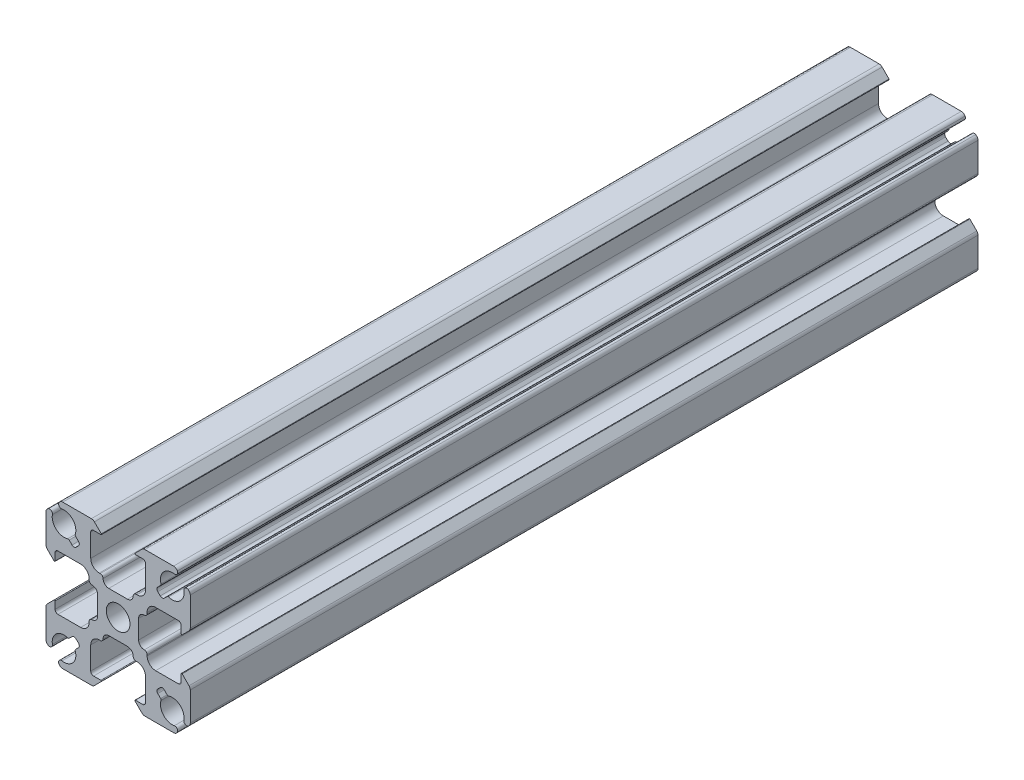
SolidWorks part; units mm, degrees
ref_plane "Front Plane" through (0, 0, 0) normal (0, 0, 1) x (1, 0, 0)
ref_plane "Top Plane" through (0, 0, 0) normal (0, 1, 0) x (1, 0, 0)
ref_plane "Right Plane" through (0, 0, 0) normal (1, 0, 0) x (0, 0, -1)
ref_plane "Plane1" through (0, 0, 0) normal (0, 0, -1) x (-1, 0, 0)
sketch "Sketch1" plane through (0, 0, 0) normal (0, 0, -1) x (-1, 0, 0)
  line L0 (-7.4885, 8.6199) -> (-6.9856, 8.117)
  line L1 (-6.9856, 7.4099) -> (-7.4099, 6.9856)
  line L2 (-8.117, 6.9856) -> (-8.6199, 7.4885)
  line L3 (-12.7, 9.7594) -> (-12.7, 4.7107)
  line L4 (-12.4803, 4.1803) -> (-11.2707, 2.9707)
  line L5 (-11.1, 3.0414) -> (-11.1, 4.325)
  line L6 (-10.6, 4.825) -> (-6.6, 4.825)
  line L7 (-5.1, 3.325) -> (-5.1, 3.15)
  line L8 (-3.6, 1.65) -> (-3.6, -1.65)
  line L9 (-5.1, -3.15) -> (-5.1, -3.325)
  line L10 (-6.6, -4.825) -> (-10.6, -4.825)
  line L11 (-11.1, -4.325) -> (-11.1, -3.0414)
  line L12 (-11.2707, -2.9707) -> (-12.4803, -4.1803)
  line L13 (-12.7, -4.7107) -> (-12.7, -9.7594)
  line L14 (-8.6199, -7.4885) -> (-8.117, -6.9856)
  line L15 (-7.4099, -6.9856) -> (-6.9856, -7.4099)
  line L16 (-6.9856, -8.117) -> (-7.4885, -8.6199)
  line L17 (-9.7594, -12.7) -> (-4.7107, -12.7)
  line L18 (-4.1803, -12.4803) -> (-2.9707, -11.2707)
  line L19 (-3.0414, -11.1) -> (-4.325, -11.1)
  line L20 (-4.825, -10.6) -> (-4.825, -6.6)
  line L21 (-3.325, -5.1) -> (-3.15, -5.1)
  line L22 (-1.65, -3.6) -> (1.65, -3.6)
  line L23 (3.15, -5.1) -> (3.325, -5.1)
  line L24 (4.825, -6.6) -> (4.825, -10.6)
  line L25 (4.325, -11.1) -> (3.0414, -11.1)
  line L26 (2.9707, -11.2707) -> (4.1803, -12.4803)
  line L27 (4.7107, -12.7) -> (9.7594, -12.7)
  line L28 (7.4885, -8.6199) -> (6.9856, -8.117)
  line L29 (6.9856, -7.4099) -> (7.4099, -6.9856)
  line L30 (8.117, -6.9856) -> (8.6199, -7.4885)
  line L31 (12.7, -9.7594) -> (12.7, -4.7107)
  line L32 (12.4803, -4.1803) -> (11.2707, -2.9707)
  line L33 (11.1, -3.0414) -> (11.1, -4.325)
  line L34 (10.6, -4.825) -> (6.6, -4.825)
  line L35 (5.1, -3.325) -> (5.1, -3.15)
  line L36 (3.6, -1.65) -> (3.6, 1.65)
  line L37 (5.1, 3.15) -> (5.1, 3.325)
  line L38 (6.6, 4.825) -> (10.6, 4.825)
  line L39 (11.1, 4.325) -> (11.1, 3.0414)
  line L40 (11.2707, 2.9707) -> (12.4803, 4.1803)
  line L41 (12.7, 4.7107) -> (12.7, 9.7594)
  line L42 (8.6199, 7.4885) -> (8.117, 6.9856)
  line L43 (7.4099, 6.9856) -> (6.9856, 7.4099)
  line L44 (6.9856, 8.117) -> (7.4885, 8.6199)
  line L45 (9.7594, 12.7) -> (4.7107, 12.7)
  line L46 (4.1803, 12.4803) -> (2.9707, 11.2707)
  line L47 (3.0414, 11.1) -> (4.325, 11.1)
  line L48 (4.825, 10.6) -> (4.825, 6.6)
  line L49 (3.325, 5.1) -> (3.15, 5.1)
  line L50 (1.65, 3.6) -> (-1.65, 3.6)
  line L51 (-3.15, 5.1) -> (-3.325, 5.1)
  line L52 (-4.825, 6.6) -> (-4.825, 10.6)
  line L53 (-4.325, 11.1) -> (-3.0414, 11.1)
  line L54 (-2.9707, 11.2707) -> (-4.1803, 12.4803)
  line L55 (-4.7107, 12.7) -> (-9.7594, 12.7)
  circle A0 centre (0, 0) radius 2.08
  arc A1 (-9.7594, 12.7) -> (-10.4266, 12.2927) centre (-9.7594, 11.95) ccw
  arc A2 (-10.4266, 12.2927) -> (-9.8933, 11.5721) centre (-9.9818, 12.0642) ccw
  arc A3 (-9.8933, 11.5721) -> (-7.5492, 8.8748) centre (-9.525, 9.525) cw
  arc A4 (-7.5492, 8.8748) -> (-7.4885, 8.6199) centre (-7.3118, 8.7967) ccw
  arc A5 (-6.9856, 8.117) -> (-6.9856, 7.4099) centre (-7.3392, 7.7635) cw
  arc A6 (-7.4099, 6.9856) -> (-8.117, 6.9856) centre (-7.7635, 7.3392) cw
  arc A7 (-8.6199, 7.4885) -> (-8.8748, 7.5492) centre (-8.7967, 7.3118) ccw
  arc A8 (-8.8748, 7.5492) -> (-11.5721, 9.8933) centre (-9.525, 9.525) cw
  arc A9 (-11.5721, 9.8933) -> (-12.2927, 10.4266) centre (-12.0642, 9.9818) ccw
  arc A10 (-12.2927, 10.4266) -> (-12.7, 9.7594) centre (-11.95, 9.7594) ccw
  arc A11 (-12.7, 4.7107) -> (-12.4803, 4.1803) centre (-11.95, 4.7107) ccw
  arc A12 (-11.2707, 2.9707) -> (-11.1, 3.0414) centre (-11.2, 3.0414) ccw
  arc A13 (-11.1, 4.325) -> (-10.6, 4.825) centre (-10.6, 4.325) cw
  arc A14 (-6.6, 4.825) -> (-5.1, 3.325) centre (-6.6, 3.325) cw
  arc A15 (-5.1, 3.15) -> (-4.6, 2.65) centre (-4.6, 3.15) ccw
  arc A16 (-4.6, 2.65) -> (-3.6, 1.65) centre (-4.6, 1.65) cw
  arc A17 (-3.6, -1.65) -> (-4.6, -2.65) centre (-4.6, -1.65) cw
  arc A18 (-4.6, -2.65) -> (-5.1, -3.15) centre (-4.6, -3.15) ccw
  arc A19 (-5.1, -3.325) -> (-6.6, -4.825) centre (-6.6, -3.325) cw
  arc A20 (-10.6, -4.825) -> (-11.1, -4.325) centre (-10.6, -4.325) cw
  arc A21 (-11.1, -3.0414) -> (-11.2707, -2.9707) centre (-11.2, -3.0414) ccw
  arc A22 (-12.4803, -4.1803) -> (-12.7, -4.7107) centre (-11.95, -4.7107) ccw
  arc A23 (-12.7, -9.7594) -> (-12.2927, -10.4266) centre (-11.95, -9.7594) ccw
  arc A24 (-12.2927, -10.4266) -> (-11.5721, -9.8933) centre (-12.0642, -9.9818) ccw
  arc A25 (-11.5721, -9.8933) -> (-8.8748, -7.5492) centre (-9.525, -9.525) cw
  arc A26 (-8.8748, -7.5492) -> (-8.6199, -7.4885) centre (-8.7967, -7.3118) ccw
  arc A27 (-8.117, -6.9856) -> (-7.4099, -6.9856) centre (-7.7635, -7.3392) cw
  arc A28 (-6.9856, -7.4099) -> (-6.9856, -8.117) centre (-7.3392, -7.7635) cw
  arc A29 (-7.4885, -8.6199) -> (-7.5492, -8.8748) centre (-7.3118, -8.7967) ccw
  arc A30 (-7.5492, -8.8748) -> (-9.8933, -11.5721) centre (-9.525, -9.525) cw
  arc A31 (-9.8933, -11.5721) -> (-10.4266, -12.2927) centre (-9.9818, -12.0642) ccw
  arc A32 (-10.4266, -12.2927) -> (-9.7594, -12.7) centre (-9.7594, -11.95) ccw
  arc A33 (-4.7107, -12.7) -> (-4.1803, -12.4803) centre (-4.7107, -11.95) ccw
  arc A34 (-2.9707, -11.2707) -> (-3.0414, -11.1) centre (-3.0414, -11.2) ccw
  arc A35 (-4.325, -11.1) -> (-4.825, -10.6) centre (-4.325, -10.6) cw
  arc A36 (-4.825, -6.6) -> (-3.325, -5.1) centre (-3.325, -6.6) cw
  arc A37 (-3.15, -5.1) -> (-2.65, -4.6) centre (-3.15, -4.6) ccw
  arc A38 (-2.65, -4.6) -> (-1.65, -3.6) centre (-1.65, -4.6) cw
  arc A39 (1.65, -3.6) -> (2.65, -4.6) centre (1.65, -4.6) cw
  arc A40 (2.65, -4.6) -> (3.15, -5.1) centre (3.15, -4.6) ccw
  arc A41 (3.325, -5.1) -> (4.825, -6.6) centre (3.325, -6.6) cw
  arc A42 (4.825, -10.6) -> (4.325, -11.1) centre (4.325, -10.6) cw
  arc A43 (3.0414, -11.1) -> (2.9707, -11.2707) centre (3.0414, -11.2) ccw
  arc A44 (4.1803, -12.4803) -> (4.7107, -12.7) centre (4.7107, -11.95) ccw
  arc A45 (9.7594, -12.7) -> (10.4266, -12.2927) centre (9.7594, -11.95) ccw
  arc A46 (10.4266, -12.2927) -> (9.8933, -11.5721) centre (9.9818, -12.0642) ccw
  arc A47 (9.8933, -11.5721) -> (7.5492, -8.8748) centre (9.525, -9.525) cw
  arc A48 (7.5492, -8.8748) -> (7.4885, -8.6199) centre (7.3118, -8.7967) ccw
  arc A49 (6.9856, -8.117) -> (6.9856, -7.4099) centre (7.3392, -7.7635) cw
  arc A50 (7.4099, -6.9856) -> (8.117, -6.9856) centre (7.7635, -7.3392) cw
  arc A51 (8.6199, -7.4885) -> (8.8748, -7.5492) centre (8.7967, -7.3118) ccw
  arc A52 (8.8748, -7.5492) -> (11.5721, -9.8933) centre (9.525, -9.525) cw
  arc A53 (11.5721, -9.8933) -> (12.2927, -10.4266) centre (12.0642, -9.9818) ccw
  arc A54 (12.2927, -10.4266) -> (12.7, -9.7594) centre (11.95, -9.7594) ccw
  arc A55 (12.7, -4.7107) -> (12.4803, -4.1803) centre (11.95, -4.7107) ccw
  arc A56 (11.2707, -2.9707) -> (11.1, -3.0414) centre (11.2, -3.0414) ccw
  arc A57 (11.1, -4.325) -> (10.6, -4.825) centre (10.6, -4.325) cw
  arc A58 (6.6, -4.825) -> (5.1, -3.325) centre (6.6, -3.325) cw
  arc A59 (5.1, -3.15) -> (4.6, -2.65) centre (4.6, -3.15) ccw
  arc A60 (4.6, -2.65) -> (3.6, -1.65) centre (4.6, -1.65) cw
  arc A61 (3.6, 1.65) -> (4.6, 2.65) centre (4.6, 1.65) cw
  arc A62 (4.6, 2.65) -> (5.1, 3.15) centre (4.6, 3.15) ccw
  arc A63 (5.1, 3.325) -> (6.6, 4.825) centre (6.6, 3.325) cw
  arc A64 (10.6, 4.825) -> (11.1, 4.325) centre (10.6, 4.325) cw
  arc A65 (11.1, 3.0414) -> (11.2707, 2.9707) centre (11.2, 3.0414) ccw
  arc A66 (12.4803, 4.1803) -> (12.7, 4.7107) centre (11.95, 4.7107) ccw
  arc A67 (12.7, 9.7594) -> (12.2927, 10.4266) centre (11.95, 9.7594) ccw
  arc A68 (12.2927, 10.4266) -> (11.5721, 9.8933) centre (12.0642, 9.9818) ccw
  arc A69 (11.5721, 9.8933) -> (8.8748, 7.5492) centre (9.525, 9.525) cw
  arc A70 (8.8748, 7.5492) -> (8.6199, 7.4885) centre (8.7967, 7.3118) ccw
  arc A71 (8.117, 6.9856) -> (7.4099, 6.9856) centre (7.7635, 7.3392) cw
  arc A72 (6.9856, 7.4099) -> (6.9856, 8.117) centre (7.3392, 7.7635) cw
  arc A73 (7.4885, 8.6199) -> (7.5492, 8.8748) centre (7.3118, 8.7967) ccw
  arc A74 (7.5492, 8.8748) -> (9.8933, 11.5721) centre (9.525, 9.525) cw
  arc A75 (9.8933, 11.5721) -> (10.4266, 12.2927) centre (9.9818, 12.0642) ccw
  arc A76 (10.4266, 12.2927) -> (9.7594, 12.7) centre (9.7594, 11.95) ccw
  arc A77 (4.7107, 12.7) -> (4.1803, 12.4803) centre (4.7107, 11.95) ccw
  arc A78 (2.9707, 11.2707) -> (3.0414, 11.1) centre (3.0414, 11.2) ccw
  arc A79 (4.325, 11.1) -> (4.825, 10.6) centre (4.325, 10.6) cw
  arc A80 (4.825, 6.6) -> (3.325, 5.1) centre (3.325, 6.6) cw
  arc A81 (3.15, 5.1) -> (2.65, 4.6) centre (3.15, 4.6) ccw
  arc A82 (2.65, 4.6) -> (1.65, 3.6) centre (1.65, 4.6) cw
  arc A83 (-1.65, 3.6) -> (-2.65, 4.6) centre (-1.65, 4.6) cw
  arc A84 (-2.65, 4.6) -> (-3.15, 5.1) centre (-3.15, 4.6) ccw
  arc A85 (-3.325, 5.1) -> (-4.825, 6.6) centre (-3.325, 6.6) cw
  arc A86 (-4.825, 10.6) -> (-4.325, 11.1) centre (-4.325, 10.6) cw
  arc A87 (-3.0414, 11.1) -> (-2.9707, 11.2707) centre (-3.0414, 11.2) ccw
  arc A88 (-4.1803, 12.4803) -> (-4.7107, 12.7) centre (-4.7107, 11.95) ccw
extrude "Boss-Extrude1" add sketch "Sketch1" against normal mid plane 138.683
sketch "Sketch2" plane through (3.6, 0, 0) normal (1, 0, 0) x (0, 0, -1)
  line L0 (69.3415, 1.65) -> (69.3415, -1.65) construction
  circle A0 centre (56.6415, 0) radius 3.025
  circle A1 centre (5.8415, 0) radius 3.025
  point P4 (69.3415, 0)
  point P7 (69.3415, 0)
  dimension "D1" = 6.05
  dimension "D2" = 6.05
  dimension "D3" = 12.7
  dimension "D4" = 63.5
extrude "Cut-Extrude1" cut sketch "Sketch2" against normal through all
